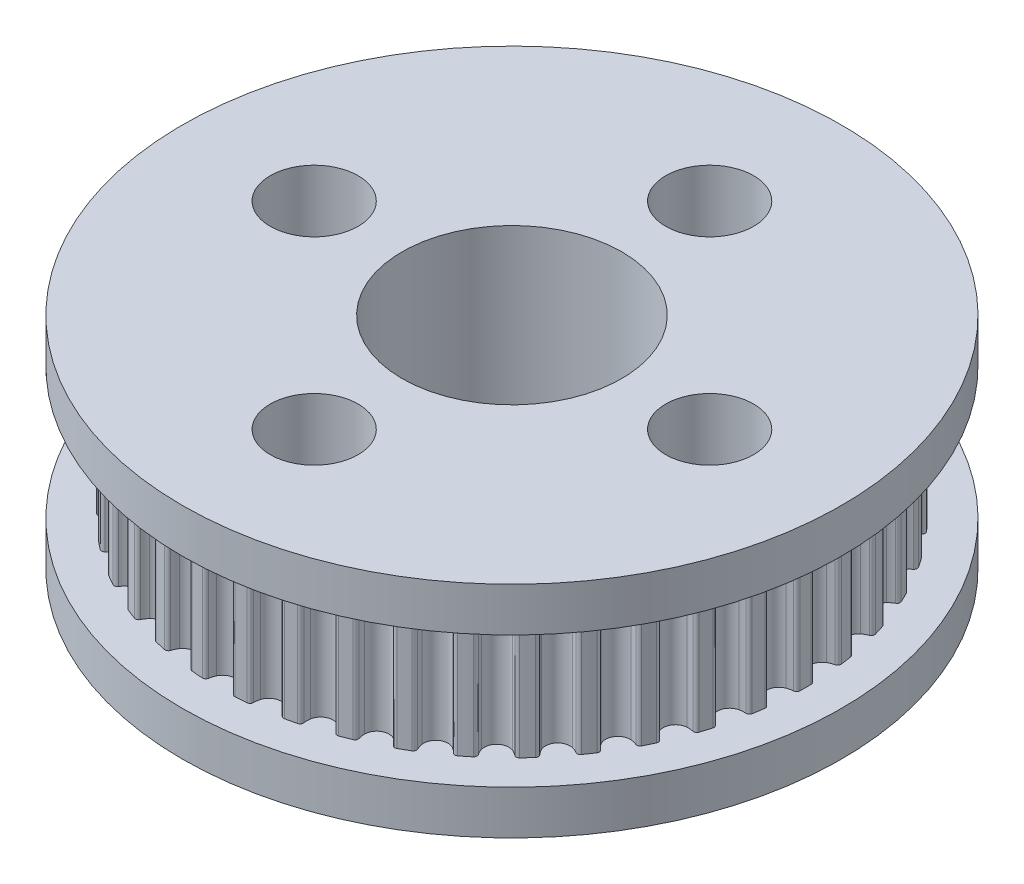
SolidWorks part; units mm, degrees
ref_plane "Front Plane" through (0, 0, 0) normal (0, 0, 1) x (1, 0, 0)
ref_plane "Top Plane" through (0, 0, 0) normal (0, 1, 0) x (1, 0, 0)
ref_plane "Right Plane" through (0, 0, 0) normal (1, 0, 0) x (0, 0, -1)
sketch "Sketch2" plane through (0, 0, 0) normal (0, 1, 0) x (1, 0, 0)
  arc A0 (-0.7447, 13.3442) -> (0.7447, 13.3442) centre (0, 0) ccw
  arc A1 (-0.5031, 12.9334) -> (0.5031, 12.9334) centre (0, 13.17) ccw
  arc A2 (0.5031, 12.9334) -> (0.5879, 13.2159) centre (-0.4018, 13.359) ccw
  arc A3 (-0.5879, 13.2159) -> (-0.5031, 12.9334) centre (0.4018, 13.359) ccw
  arc A4 (-0.7447, 13.3442) -> (-0.5879, 13.2159) centre (-0.7364, 13.1945) cw
  arc A5 (0.7447, 13.3442) -> (0.5879, 13.2159) centre (0.7364, 13.1945) ccw
  arc A6 (1.2524, 13.3062) -> (1.3884, 13.1559) centre (1.2384, 13.1568) cw
  arc A7 (1.3884, 13.1559) -> (1.4301, 12.8639) centre (2.3883, 13.1499) ccw
  arc A8 (1.4301, 12.8639) -> (2.4251, 12.7139) centre (1.9629, 13.0229) ccw
  arc A9 (2.4251, 12.7139) -> (2.5511, 12.9807) centre (1.5938, 13.2696) ccw
  arc A10 (2.7253, 13.0842) -> (2.5511, 12.9807) centre (2.6947, 12.9373) ccw
  arc A11 (3.2216, 12.9709) -> (3.3336, 12.8021) centre (3.1855, 12.8253) cw
  arc A12 (3.3336, 12.8021) -> (3.3314, 12.5071) centre (4.3216, 12.647) ccw
  arc A13 (3.3314, 12.5071) -> (4.293, 12.2105) centre (3.8819, 12.5849) ccw
  arc A14 (4.293, 12.2105) -> (4.4573, 12.4555) centre (3.5537, 12.8839) ccw
  arc A15 (4.6449, 12.5319) -> (4.4573, 12.4555) centre (4.5928, 12.3912) ccw
  arc A16 (5.1188, 12.3459) -> (5.2045, 12.1622) centre (5.0614, 12.2073) cw
  arc A17 (5.2045, 12.1622) -> (5.1583, 11.8709) centre (6.1582, 11.8617) ccw
  arc A18 (5.1583, 11.8709) -> (6.0649, 11.4343) centre (5.7142, 11.8658) ccw
  arc A19 (6.0649, 11.4343) -> (6.2639, 11.652) centre (5.4342, 12.2103) ccw
  arc A20 (6.4608, 11.6996) -> (6.2639, 11.652) centre (6.3883, 11.5683) ccw
  arc A21 (6.9017, 11.4451) -> (6.959, 11.2507) centre (6.8243, 11.3166) cw
  arc A22 (6.959, 11.2507) -> (6.8699, 10.9695) centre (7.8573, 10.8114) ccw
  arc A23 (6.8699, 10.9695) -> (7.7013, 10.4026) centre (7.4189, 10.8816) ccw
  arc A24 (7.7013, 10.4026) -> (7.9306, 10.5883) centre (7.1934, 11.264) ccw
  arc A25 (8.1324, 10.606) -> (7.9306, 10.5883) centre (8.0411, 10.487) ccw
  arc A26 (8.5304, 10.2886) -> (8.5581, 10.0879) centre (8.4347, 10.1731) cw
  arc A27 (8.5581, 10.0879) -> (8.4281, 9.8231) centre (9.3809, 9.5195) ccw
  arc A28 (8.4281, 9.8231) -> (9.1658, 9.1386) centre (8.9579, 9.6543) ccw
  arc A29 (9.1658, 9.1386) -> (9.4201, 9.2881) centre (8.7919, 10.0661) ccw
  arc A30 (9.6223, 9.2755) -> (9.4201, 9.2881) centre (9.5143, 9.1714) ccw
  arc A31 (9.9686, 8.9023) -> (9.9661, 8.6997) centre (9.8567, 8.8023) cw
  arc A32 (9.9661, 8.6997) -> (9.798, 8.4572) centre (10.695, 8.015) ccw
  arc A33 (9.798, 8.4572) -> (10.4254, 7.6705) centre (10.2967, 8.2114) ccw
  arc A34 (10.4254, 7.6705) -> (10.6992, 7.7803) centre (10.1939, 8.6433) ccw
  arc A35 (10.8973, 7.7377) -> (10.6992, 7.7803) centre (10.775, 7.6509) ccw
  arc A36 (11.1841, 7.3171) -> (11.1514, 7.1171) centre (11.0585, 7.235) cw
  arc A37 (11.1514, 7.1171) -> (10.9491, 6.9024) centre (11.7701, 6.3315) ccw
  arc A38 (10.9491, 6.9024) -> (11.4522, 6.031) centre (11.4056, 6.585) ccw
  arc A39 (11.4522, 6.031) -> (11.7393, 6.0988) centre (11.3683, 7.0274) ccw
  arc A40 (11.9288, 6.0271) -> (11.7393, 6.0988) centre (11.7949, 5.9595) ccw
  arc A41 (12.1497, 5.5685) -> (12.0876, 5.3756) centre (12.0133, 5.506) cw
  arc A42 (12.0876, 5.3756) -> (11.8555, 5.1934) centre (12.5823, 4.5066) ccw
  arc A43 (11.8555, 5.1934) -> (12.2232, 4.2567) centre (12.2596, 4.8115) ccw
  arc A44 (12.2232, 4.2567) -> (12.5172, 4.281) centre (12.2887, 5.2546) ccw
  arc A45 (12.6939, 4.1819) -> (12.5172, 4.281) centre (12.5514, 4.135) ccw
  arc A46 (12.8439, 3.6954) -> (12.7537, 3.514) centre (12.6998, 3.654) cw
  arc A47 (12.7537, 3.514) -> (12.4972, 3.3685) centre (13.1134, 2.5809) ccw
  arc A48 (12.4972, 3.3685) -> (12.7211, 2.3874) centre (12.8398, 2.9306) ccw
  arc A49 (12.7211, 2.3874) -> (13.0154, 2.3676) centre (12.9346, 3.3644) ccw
  arc A50 (13.1754, 2.2433) -> (13.0154, 2.3676) centre (13.0275, 2.2181) ccw
  arc A51 (13.2513, 1.7399) -> (13.135, 1.5739) centre (13.1025, 1.7204) cw
  arc A52 (13.135, 1.5739) -> (12.8596, 1.4682) centre (13.3516, 0.5977) ccw
  arc A53 (12.8596, 1.4682) -> (12.9348, 0.4648) centre (13.1332, 0.9842) ccw
  arc A54 (12.9348, 0.4648) -> (13.2229, 0.4013) centre (13.2916, 1.399) ccw
  arc A55 (13.3626, 0.2545) -> (13.2229, 0.4013) centre (13.2126, 0.2517) ccw
  arc A56 (13.3626, -0.2545) -> (13.2229, -0.4013) centre (13.2126, -0.2517) cw
  arc A57 (13.2229, -0.4013) -> (12.9348, -0.4648) centre (13.2916, -1.399) ccw
  arc A58 (12.9348, -0.4648) -> (12.8596, -1.4682) centre (13.1332, -0.9842) ccw
  arc A59 (12.8596, -1.4682) -> (13.135, -1.5739) centre (13.3516, -0.5977) ccw
  arc A60 (13.2513, -1.7399) -> (13.135, -1.5739) centre (13.1025, -1.7204) ccw
  arc A61 (13.1754, -2.2433) -> (13.0154, -2.3676) centre (13.0275, -2.2181) cw
  arc A62 (13.0154, -2.3676) -> (12.7211, -2.3874) centre (12.9346, -3.3644) ccw
  arc A63 (12.7211, -2.3874) -> (12.4972, -3.3685) centre (12.8398, -2.9306) ccw
  arc A64 (12.4972, -3.3685) -> (12.7537, -3.514) centre (13.1134, -2.5809) ccw
  arc A65 (12.8439, -3.6954) -> (12.7537, -3.514) centre (12.6998, -3.654) ccw
  arc A66 (12.6939, -4.1819) -> (12.5172, -4.281) centre (12.5514, -4.135) cw
  arc A67 (12.5172, -4.281) -> (12.2232, -4.2567) centre (12.2887, -5.2546) ccw
  arc A68 (12.2232, -4.2567) -> (11.8555, -5.1934) centre (12.2596, -4.8115) ccw
  arc A69 (11.8555, -5.1934) -> (12.0876, -5.3756) centre (12.5823, -4.5066) ccw
  arc A70 (12.1497, -5.5685) -> (12.0876, -5.3756) centre (12.0133, -5.506) ccw
  arc A71 (11.9288, -6.0271) -> (11.7393, -6.0988) centre (11.7949, -5.9595) cw
  arc A72 (11.7393, -6.0988) -> (11.4522, -6.031) centre (11.3683, -7.0274) ccw
  arc A73 (11.4522, -6.031) -> (10.9491, -6.9024) centre (11.4056, -6.585) ccw
  arc A74 (10.9491, -6.9024) -> (11.1514, -7.1171) centre (11.7701, -6.3315) ccw
  arc A75 (11.1841, -7.3171) -> (11.1514, -7.1171) centre (11.0585, -7.235) ccw
  arc A76 (10.8973, -7.7377) -> (10.6992, -7.7803) centre (10.775, -7.6509) cw
  arc A77 (10.6992, -7.7803) -> (10.4254, -7.6705) centre (10.1939, -8.6433) ccw
  arc A78 (10.4254, -7.6705) -> (9.798, -8.4572) centre (10.2967, -8.2114) ccw
  arc A79 (9.798, -8.4572) -> (9.9661, -8.6997) centre (10.695, -8.015) ccw
  arc A80 (9.9686, -8.9023) -> (9.9661, -8.6997) centre (9.8567, -8.8023) ccw
  arc A81 (9.6223, -9.2755) -> (9.4201, -9.2881) centre (9.5143, -9.1714) cw
  arc A82 (9.4201, -9.2881) -> (9.1658, -9.1386) centre (8.7919, -10.0661) ccw
  arc A83 (9.1658, -9.1386) -> (8.4281, -9.8231) centre (8.9579, -9.6543) ccw
  arc A84 (8.4281, -9.8231) -> (8.5581, -10.0879) centre (9.3809, -9.5195) ccw
  arc A85 (8.5304, -10.2886) -> (8.5581, -10.0879) centre (8.4347, -10.1731) ccw
  arc A86 (8.1324, -10.606) -> (7.9306, -10.5883) centre (8.0411, -10.487) cw
  arc A87 (7.9306, -10.5883) -> (7.7013, -10.4026) centre (7.1934, -11.264) ccw
  arc A88 (7.7013, -10.4026) -> (6.8699, -10.9695) centre (7.4189, -10.8816) ccw
  arc A89 (6.8699, -10.9695) -> (6.959, -11.2507) centre (7.8573, -10.8114) ccw
  arc A90 (6.9017, -11.4451) -> (6.959, -11.2507) centre (6.8243, -11.3166) ccw
  arc A91 (6.4608, -11.6996) -> (6.2639, -11.652) centre (6.3883, -11.5683) cw
  arc A92 (6.2639, -11.652) -> (6.0649, -11.4343) centre (5.4342, -12.2103) ccw
  arc A93 (6.0649, -11.4343) -> (5.1583, -11.8709) centre (5.7142, -11.8658) ccw
  arc A94 (5.1583, -11.8709) -> (5.2045, -12.1622) centre (6.1582, -11.8617) ccw
  arc A95 (5.1188, -12.3459) -> (5.2045, -12.1622) centre (5.0614, -12.2073) ccw
  arc A96 (4.6449, -12.5319) -> (4.4573, -12.4555) centre (4.5928, -12.3912) cw
  arc A97 (4.4573, -12.4555) -> (4.293, -12.2105) centre (3.5537, -12.8839) ccw
  arc A98 (4.293, -12.2105) -> (3.3314, -12.5071) centre (3.8819, -12.5849) ccw
  arc A99 (3.3314, -12.5071) -> (3.3336, -12.8021) centre (4.3216, -12.647) ccw
  arc A100 (3.2216, -12.9709) -> (3.3336, -12.8021) centre (3.1855, -12.8253) ccw
  arc A101 (2.7253, -13.0842) -> (2.5511, -12.9807) centre (2.6947, -12.9373) cw
  arc A102 (2.5511, -12.9807) -> (2.4251, -12.7139) centre (1.5938, -13.2696) ccw
  arc A103 (2.4251, -12.7139) -> (1.4301, -12.8639) centre (1.9629, -13.0229) ccw
  arc A104 (1.4301, -12.8639) -> (1.3884, -13.1559) centre (2.3883, -13.1499) ccw
  arc A105 (1.2524, -13.3062) -> (1.3884, -13.1559) centre (1.2384, -13.1568) ccw
  arc A106 (0.7447, -13.3442) -> (0.5879, -13.2159) centre (0.7364, -13.1945) cw
  arc A107 (0.5879, -13.2159) -> (0.5031, -12.9334) centre (-0.4018, -13.359) ccw
  arc A108 (0.5031, -12.9334) -> (-0.5031, -12.9334) centre (0, -13.17) ccw
  arc A109 (-0.5031, -12.9334) -> (-0.5879, -13.2159) centre (0.4018, -13.359) ccw
  arc A110 (-0.7447, -13.3442) -> (-0.5879, -13.2159) centre (-0.7364, -13.1945) ccw
  arc A111 (-1.2524, -13.3062) -> (-1.3884, -13.1559) centre (-1.2384, -13.1568) cw
  arc A112 (-1.3884, -13.1559) -> (-1.4301, -12.8639) centre (-2.3883, -13.1499) ccw
  arc A113 (-1.4301, -12.8639) -> (-2.4251, -12.7139) centre (-1.9629, -13.0229) ccw
  arc A114 (-2.4251, -12.7139) -> (-2.5511, -12.9807) centre (-1.5938, -13.2696) ccw
  arc A115 (-2.7253, -13.0842) -> (-2.5511, -12.9807) centre (-2.6947, -12.9373) ccw
  arc A116 (-3.2216, -12.9709) -> (-3.3336, -12.8021) centre (-3.1855, -12.8253) cw
  arc A117 (-3.3336, -12.8021) -> (-3.3314, -12.5071) centre (-4.3216, -12.647) ccw
  arc A118 (-3.3314, -12.5071) -> (-4.293, -12.2105) centre (-3.8819, -12.5849) ccw
  arc A119 (-4.293, -12.2105) -> (-4.4573, -12.4555) centre (-3.5537, -12.8839) ccw
  arc A120 (-4.6449, -12.5319) -> (-4.4573, -12.4555) centre (-4.5928, -12.3912) ccw
  arc A121 (-5.1188, -12.3459) -> (-5.2045, -12.1622) centre (-5.0614, -12.2073) cw
  arc A122 (-5.2045, -12.1622) -> (-5.1583, -11.8709) centre (-6.1582, -11.8617) ccw
  arc A123 (-5.1583, -11.8709) -> (-6.0649, -11.4343) centre (-5.7142, -11.8658) ccw
  arc A124 (-6.0649, -11.4343) -> (-6.2639, -11.652) centre (-5.4342, -12.2103) ccw
  arc A125 (-6.4608, -11.6996) -> (-6.2639, -11.652) centre (-6.3883, -11.5683) ccw
  arc A126 (-6.9017, -11.4451) -> (-6.959, -11.2507) centre (-6.8243, -11.3166) cw
  arc A127 (-6.959, -11.2507) -> (-6.8699, -10.9695) centre (-7.8573, -10.8114) ccw
  arc A128 (-6.8699, -10.9695) -> (-7.7013, -10.4026) centre (-7.4189, -10.8816) ccw
  arc A129 (-7.7013, -10.4026) -> (-7.9306, -10.5883) centre (-7.1934, -11.264) ccw
  arc A130 (-8.1324, -10.606) -> (-7.9306, -10.5883) centre (-8.0411, -10.487) ccw
  arc A131 (-8.5304, -10.2886) -> (-8.5581, -10.0879) centre (-8.4347, -10.1731) cw
  arc A132 (-8.5581, -10.0879) -> (-8.4281, -9.8231) centre (-9.3809, -9.5195) ccw
  arc A133 (-8.4281, -9.8231) -> (-9.1658, -9.1386) centre (-8.9579, -9.6543) ccw
  arc A134 (-9.1658, -9.1386) -> (-9.4201, -9.2881) centre (-8.7919, -10.0661) ccw
  arc A135 (-9.6223, -9.2755) -> (-9.4201, -9.2881) centre (-9.5143, -9.1714) ccw
  arc A136 (-9.9686, -8.9023) -> (-9.9661, -8.6997) centre (-9.8567, -8.8023) cw
  arc A137 (-9.9661, -8.6997) -> (-9.798, -8.4572) centre (-10.695, -8.015) ccw
  arc A138 (-9.798, -8.4572) -> (-10.4254, -7.6705) centre (-10.2967, -8.2114) ccw
  arc A139 (-10.4254, -7.6705) -> (-10.6992, -7.7803) centre (-10.1939, -8.6433) ccw
  arc A140 (-10.8973, -7.7377) -> (-10.6992, -7.7803) centre (-10.775, -7.6509) ccw
  arc A141 (-11.1841, -7.3171) -> (-11.1514, -7.1171) centre (-11.0585, -7.235) cw
  arc A142 (-11.1514, -7.1171) -> (-10.9491, -6.9024) centre (-11.7701, -6.3315) ccw
  arc A143 (-10.9491, -6.9024) -> (-11.4522, -6.031) centre (-11.4056, -6.585) ccw
  arc A144 (-11.4522, -6.031) -> (-11.7393, -6.0988) centre (-11.3683, -7.0274) ccw
  arc A145 (-11.9288, -6.0271) -> (-11.7393, -6.0988) centre (-11.7949, -5.9595) ccw
  arc A146 (-12.1497, -5.5685) -> (-12.0876, -5.3756) centre (-12.0133, -5.506) cw
  arc A147 (-12.0876, -5.3756) -> (-11.8555, -5.1934) centre (-12.5823, -4.5066) ccw
  arc A148 (-11.8555, -5.1934) -> (-12.2232, -4.2567) centre (-12.2596, -4.8115) ccw
  arc A149 (-12.2232, -4.2567) -> (-12.5172, -4.281) centre (-12.2887, -5.2546) ccw
  arc A150 (-12.6939, -4.1819) -> (-12.5172, -4.281) centre (-12.5514, -4.135) ccw
  arc A151 (-12.8439, -3.6954) -> (-12.7537, -3.514) centre (-12.6998, -3.654) cw
  arc A152 (-12.7537, -3.514) -> (-12.4972, -3.3685) centre (-13.1134, -2.5809) ccw
  arc A153 (-12.4972, -3.3685) -> (-12.7211, -2.3874) centre (-12.8398, -2.9306) ccw
  arc A154 (-12.7211, -2.3874) -> (-13.0154, -2.3676) centre (-12.9346, -3.3644) ccw
  arc A155 (-13.1754, -2.2433) -> (-13.0154, -2.3676) centre (-13.0275, -2.2181) ccw
  arc A156 (-13.2513, -1.7399) -> (-13.135, -1.5739) centre (-13.1025, -1.7204) cw
  arc A157 (-13.135, -1.5739) -> (-12.8596, -1.4682) centre (-13.3516, -0.5977) ccw
  arc A158 (-12.8596, -1.4682) -> (-12.9348, -0.4648) centre (-13.1332, -0.9842) ccw
  arc A159 (-12.9348, -0.4648) -> (-13.2229, -0.4013) centre (-13.2916, -1.399) ccw
  arc A160 (-13.3626, -0.2545) -> (-13.2229, -0.4013) centre (-13.2126, -0.2517) ccw
  arc A161 (-13.3626, 0.2545) -> (-13.2229, 0.4013) centre (-13.2126, 0.2517) cw
  arc A162 (-13.2229, 0.4013) -> (-12.9348, 0.4648) centre (-13.2916, 1.399) ccw
  arc A163 (-12.9348, 0.4648) -> (-12.8596, 1.4682) centre (-13.1332, 0.9842) ccw
  arc A164 (-12.8596, 1.4682) -> (-13.135, 1.5739) centre (-13.3516, 0.5977) ccw
  arc A165 (-13.2513, 1.7399) -> (-13.135, 1.5739) centre (-13.1025, 1.7204) ccw
  arc A166 (-13.1754, 2.2433) -> (-13.0154, 2.3676) centre (-13.0275, 2.2181) cw
  arc A167 (-13.0154, 2.3676) -> (-12.7211, 2.3874) centre (-12.9346, 3.3644) ccw
  arc A168 (-12.7211, 2.3874) -> (-12.4972, 3.3685) centre (-12.8398, 2.9306) ccw
  arc A169 (-12.4972, 3.3685) -> (-12.7537, 3.514) centre (-13.1134, 2.5809) ccw
  arc A170 (-12.8439, 3.6954) -> (-12.7537, 3.514) centre (-12.6998, 3.654) ccw
  arc A171 (-12.6939, 4.1819) -> (-12.5172, 4.281) centre (-12.5514, 4.135) cw
  arc A172 (-12.5172, 4.281) -> (-12.2232, 4.2567) centre (-12.2887, 5.2546) ccw
  arc A173 (-12.2232, 4.2567) -> (-11.8555, 5.1934) centre (-12.2596, 4.8115) ccw
  arc A174 (-11.8555, 5.1934) -> (-12.0876, 5.3756) centre (-12.5823, 4.5066) ccw
  arc A175 (-12.1497, 5.5685) -> (-12.0876, 5.3756) centre (-12.0133, 5.506) ccw
  arc A176 (-11.9288, 6.0271) -> (-11.7393, 6.0988) centre (-11.7949, 5.9595) cw
  arc A177 (-11.7393, 6.0988) -> (-11.4522, 6.031) centre (-11.3683, 7.0274) ccw
  arc A178 (-11.4522, 6.031) -> (-10.9491, 6.9024) centre (-11.4056, 6.585) ccw
  arc A179 (-10.9491, 6.9024) -> (-11.1514, 7.1171) centre (-11.7701, 6.3315) ccw
  arc A180 (-11.1841, 7.3171) -> (-11.1514, 7.1171) centre (-11.0585, 7.235) ccw
  arc A181 (-10.8973, 7.7377) -> (-10.6992, 7.7803) centre (-10.775, 7.6509) cw
  arc A182 (-10.6992, 7.7803) -> (-10.4254, 7.6705) centre (-10.1939, 8.6433) ccw
  arc A183 (-10.4254, 7.6705) -> (-9.798, 8.4572) centre (-10.2967, 8.2114) ccw
  arc A184 (-9.798, 8.4572) -> (-9.9661, 8.6997) centre (-10.695, 8.015) ccw
  arc A185 (-9.9686, 8.9023) -> (-9.9661, 8.6997) centre (-9.8567, 8.8023) ccw
  arc A186 (-9.6223, 9.2755) -> (-9.4201, 9.2881) centre (-9.5143, 9.1714) cw
  arc A187 (-9.4201, 9.2881) -> (-9.1658, 9.1386) centre (-8.7919, 10.0661) ccw
  arc A188 (-9.1658, 9.1386) -> (-8.4281, 9.8231) centre (-8.9579, 9.6543) ccw
  arc A189 (-8.4281, 9.8231) -> (-8.5581, 10.0879) centre (-9.3809, 9.5195) ccw
  arc A190 (-8.5304, 10.2886) -> (-8.5581, 10.0879) centre (-8.4347, 10.1731) ccw
  arc A191 (-8.1324, 10.606) -> (-7.9306, 10.5883) centre (-8.0411, 10.487) cw
  arc A192 (-7.9306, 10.5883) -> (-7.7013, 10.4026) centre (-7.1934, 11.264) ccw
  arc A193 (-7.7013, 10.4026) -> (-6.8699, 10.9695) centre (-7.4189, 10.8816) ccw
  arc A194 (-6.8699, 10.9695) -> (-6.959, 11.2507) centre (-7.8573, 10.8114) ccw
  arc A195 (-6.9017, 11.4451) -> (-6.959, 11.2507) centre (-6.8243, 11.3166) ccw
  arc A196 (-6.4608, 11.6996) -> (-6.2639, 11.652) centre (-6.3883, 11.5683) cw
  arc A197 (-6.2639, 11.652) -> (-6.0649, 11.4343) centre (-5.4342, 12.2103) ccw
  arc A198 (-6.0649, 11.4343) -> (-5.1583, 11.8709) centre (-5.7142, 11.8658) ccw
  arc A199 (-5.1583, 11.8709) -> (-5.2045, 12.1622) centre (-6.1582, 11.8617) ccw
  arc A200 (-5.1188, 12.3459) -> (-5.2045, 12.1622) centre (-5.0614, 12.2073) ccw
  arc A201 (-4.6449, 12.5319) -> (-4.4573, 12.4555) centre (-4.5928, 12.3912) cw
  arc A202 (-4.4573, 12.4555) -> (-4.293, 12.2105) centre (-3.5537, 12.8839) ccw
  arc A203 (-4.293, 12.2105) -> (-3.3314, 12.5071) centre (-3.8819, 12.5849) ccw
  arc A204 (-3.3314, 12.5071) -> (-3.3336, 12.8021) centre (-4.3216, 12.647) ccw
  arc A205 (-3.2216, 12.9709) -> (-3.3336, 12.8021) centre (-3.1855, 12.8253) ccw
  arc A206 (-2.7253, 13.0842) -> (-2.5511, 12.9807) centre (-2.6947, 12.9373) cw
  arc A207 (-2.5511, 12.9807) -> (-2.4251, 12.7139) centre (-1.5938, 13.2696) ccw
  arc A208 (-2.4251, 12.7139) -> (-1.4301, 12.8639) centre (-1.9629, 13.0229) ccw
  arc A209 (-1.4301, 12.8639) -> (-1.3884, 13.1559) centre (-2.3883, 13.1499) ccw
  arc A210 (-1.2524, 13.3062) -> (-1.3884, 13.1559) centre (-1.2384, 13.1568) ccw
  point P5 (0, 13.365)
  point P468 (0, 0)
  dimension "D1" = 26.73
  dimension "D2" = 1.112
  dimension "D4" = 2
  dimension "D5" = 2
  dimension "D6" = 0.15
  dimension "D3" = 0.195
  dimension "D7" = 42
extrude "Boss-Extrude1" add sketch "Sketch2" along normal mid plane 10 contours A0 A210 A209 A208 A207 A206 A205 A204 A203 A202 A201 A200 A199 A198 A197 A196 A195 A194 A193 A192 A191 A190 A189 A188 A187 A186 A185 A184 A183 A182 A181 A180 A179 A178 A177 A176 A175 A174 A173 A172 A171 A170 A169 region at (0, 0, 0)
sketch "Sketch3" plane through (0, 5, 0) normal (0, 1, 0) x (1, 0, 0)
  circle A0 centre (0, 0) radius 15
  dimension "D1" = 30
extrude "Boss-Extrude2" add sketch "Sketch3" against normal blind 2
mirror "Mirror1" about plane through (0, 0, 0) normal (0, 1, 0) of "Boss-Extrude2"
sketch "Sketch4" plane through (0, 5, 0) normal (0, 1, 0) x (1, 0, 0)
  circle A0 centre (0, 0) radius 9
  circle A1 centre (0, 9) radius 2
  circle A2 centre (9, 0) radius 2
  circle A3 centre (0, -9) radius 2
  circle A4 centre (-9, 0) radius 2
  circle A5 centre (0, 0) radius 5
  dimension "D1" = 18
  dimension "D2" = 4
  dimension "D3" = 4
  dimension "D4" = 4
  dimension "D5" = 4
  dimension "D6" = 10
extrude "Cut-Extrude1" cut sketch "Sketch4" against normal through all contours A0 A4 | A0 A4 | A0 A1 | A0 A1 | A5 | A0 A2 | A0 A2 | A0 A3 | A0 A3 region at (8.1124, 5, 0) region at (9.8075, 5, 0) region at (0, 5, -8.1124) region at (0, 5, -9.8075) region at (0, 5, 9.8075) region at (0, 5, 8.1124) region at (-8.1124, 5, 0) region at (-9.8075, 5, 0) region at (0, 5, 0)
sketch "Sketch5" plane through (0, -5, 0) normal (0, -1, 0) x (1, 0, 0)
  circle A0 centre (0, 9) radius 3.5
  circle A1 centre (9, 0) radius 3.5
  circle A2 centre (0, -9) radius 3.5
  circle A3 centre (-9, 0) radius 3.5
  dimension "D1" = 7
  dimension "D2" = 7
  dimension "D3" = 7
  dimension "D4" = 7
extrude "Cut-Extrude2" cut sketch "Sketch5" against normal blind 2
